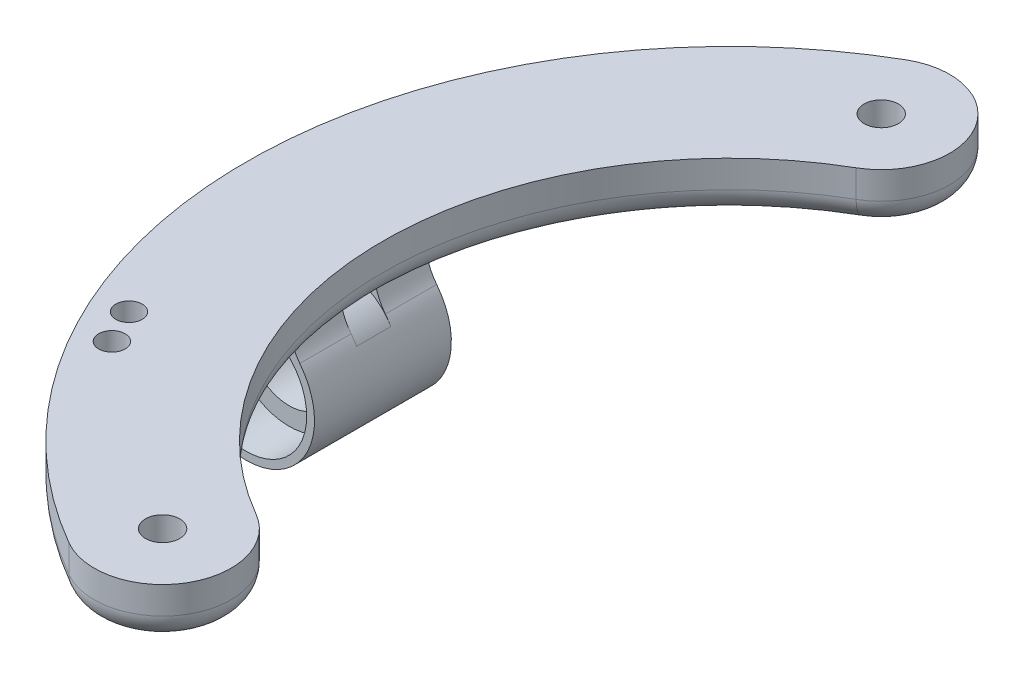
SolidWorks part; units mm, degrees
ref_plane "Front Plane" through (0, 0, 0) normal (0, 0, 1) x (1, 0, 0)
ref_plane "Top Plane" through (0, 0, 0) normal (0, 1, 0) x (1, 0, 0)
ref_plane "Right Plane" through (0, 0, 0) normal (1, 0, 0) x (0, 0, -1)
sketch "Sketch1" plane through (0, 0, 0) normal (0, 0, 1) x (1, 0, 0)
  line L0 (0, -6.6146) -> (0, 6.6146) construction
  line L1 (-64.2938, 0) -> (-64.2938, -5.08)
  line L2 (-69.0563, -9.8425) -> (-84.9312, -9.8425)
  line L3 (-89.6937, -5.08) -> (-89.6937, 0)
  line L4 (-89.6937, 0) -> (-64.2938, 0)
  line L5 (64.4709, -12.0559) -> (-64.2938, -9.8425) construction
  arc A0 (-84.9312, -9.8425) -> (-89.6937, -5.08) centre (-84.9312, -5.08) cw
  arc A1 (-69.0563, -9.8425) -> (-64.2938, -5.08) centre (-69.0563, -5.08) ccw
  point P4 (0, 0)
  point P8 (0, 0)
  point P12 (-89.6937, -9.8425)
  dimension "D4" = 4.7625
  dimension "D1" = 25.4
  dimension "D2" = 9.8425
  dimension "D3" = 128.5875
revolve "MainAttachmentRing" add sketch "Sketch1" angle 360 about L0
sketch "Sketch2" plane through (0, 0, 0) normal (0, 0, 1) x (1, 0, 0)
  line L5 (-76.9938, -9.8425) -> (-76.9938, -22.5425) construction
  line L6 (-76.9938, -22.5425) -> (-76.9938, -39.878) construction
  line L7 (0, 0) -> (0, -9.8425) construction
  line L8 (0, -9.8425) -> (-76.9938, -9.8425) construction
  line L9 (-69.0563, -8.7943) -> (-69.0563, -3.4925)
  line L10 (-69.0563, -9.8425) -> (-84.9312, -9.8425) construction
  line L11 (-84.9312, -8.7943) -> (-84.9312, -3.4925)
  line L13 (-69.0563, -9.8425) -> (69.0563, -9.8425) construction
  line L14 (-69.0563, -9.8425) -> (69.0563, -9.8425) construction
  line L18 (-84.9312, -9.8425) -> (84.9312, -9.8425) construction
  line L19 (-84.9312, -9.8425) -> (84.9312, -9.8425) construction
  line L20 (-69.0563, -3.4925) -> (-84.9312, -3.4925)
  line L21 (-84.9312, -31.9405) -> (-84.9312, -24.325) construction
  line L22 (-84.9312, -24.325) -> (-84.9312, -23.2606) construction
  line L24 (-69.0563, -24.325) -> (-69.0563, -23.2606) construction
  line L25 (-84.9312, -23.2606) -> (-84.9312, -12.6286) construction
  line L26 (-69.0563, -23.2606) -> (-69.0563, -12.6286) construction
  circle A2 centre (-76.9938, -22.5425) radius 2.3813 construction
  arc A5 (-86.9723, -14.6864) -> (-67.0152, -14.6864) centre (-76.9938, -22.5425) ccw
  circle A6 centre (-76.9938, -22.5425) radius 8.1352 construction
  arc A7 (-69.0563, -12.6286) -> (-76.9938, -9.8425) centre (-76.9938, -22.5425) ccw construction
  circle A8 centre (-76.9938, -22.5425) radius 7.9375
  arc A9 (-76.9938, -9.8425) -> (-84.9312, -12.6286) centre (-76.9938, -22.5425) ccw construction
  arc A10 (-69.0563, -8.7943) -> (-67.0152, -14.6864) centre (-59.5313, -8.7943) ccw
  arc A11 (-84.9312, -8.7943) -> (-86.9723, -14.6864) centre (-94.4562, -8.7943) cw
  circle A12 centre (-76.9938, -22.5425) radius 4 construction
  point P6 (-76.9938, -31.9405)
  point P27 (0, 0)
  dimension "D3" = 15.875
  dimension "D4" = 4.7625
  dimension "D6" = 9.525
  dimension "D5" = 8
  dimension "D7" = 12.7
  dimension "D1" = 6.35
  dimension "D2" = 12.7
extrude "SensorArmature" add sketch "Sketch2" along normal blind 12.7 and the other way blind 12.7 contours L11 A11 A5 A10 L9 L20 A12 region at (-68.9157, -12.0452, 0)
sketch "Sketch15" plane through (0, 0, 12.7) normal (0, 0, 1) x (1, 0, 0)
  circle A0 centre (-76.9938, -22.5425) radius 11.25
  dimension "D1" = 22.5
extrude "BearingRace1" cut sketch "Sketch15" against normal blind 8
sketch "Sketch16" plane through (0, 0, -12.7) normal (0, 0, -1) x (-1, 0, 0)
  circle A0 centre (76.9938, -22.5425) radius 11.25 construction
  circle A1 centre (76.9938, -22.5425) radius 11.25
extrude "BearingRace2" cut sketch "Sketch16" against normal blind 8
sketch "Sketch6" plane through (0, 0, 0) normal (0, 1, 0) x (1, 0, 0)
  line L0 (0, 0) -> (38.4252, 0) construction
  line L1 (68.0638, -50.8) -> (128.8023, -50.8)
  line L2 (66.0722, 0) -> (128.8023, 0) construction
  line L3 (66.0722, -53.3646) -> (66.0722, -20.0805)
  line L4 (68.0638, 50.8) -> (128.8023, 50.8)
  line L5 (128.8023, -50.8) -> (128.8023, 50.8)
  line L6 (66.0722, -20.0805) -> (66.0722, 0) construction
  line L7 (66.0722, 20.0805) -> (66.0722, 53.3646)
  line L8 (66.0722, 0) -> (66.0722, 20.0805) construction
  line L9 (66.0722, 53.3646) -> (66.0722, 60.6583) construction
  line L10 (66.0722, -60.6583) -> (66.0722, -53.3646) construction
  circle A0 centre (0, 0) radius 69.0563 construction
  circle A1 centre (0, 0) radius 89.6937 construction
  arc A2 (66.0722, -20.0805) -> (66.0722, 20.0805) centre (0, 0) ccw
  arc A3 (0, 69.0563) -> (66.0722, -20.0805) centre (0, 0) ccw construction
  arc A4 (66.0722, 20.0805) -> (0, 69.0563) centre (0, 0) ccw construction
  circle A5 centre (0, 0) radius 84.9312 construction
  arc A6 (68.0638, -50.8) -> (66.0722, -53.3646) centre (0, 0) ccw
  arc A7 (84.9312, 0) -> (66.0722, 53.3646) centre (0, 0) ccw construction
  arc A8 (66.0722, 53.3646) -> (68.0638, 50.8) centre (0, 0) ccw
  arc A9 (66.0722, -53.3646) -> (84.9312, 0) centre (0, 0) ccw construction
  arc A10 (0, 84.9312) -> (68.0638, -50.8) centre (0, 0) ccw construction
  arc A11 (68.0638, 50.8) -> (0, 84.9312) centre (0, 0) ccw construction
  point P2 (0, 0)
  point P3 (0, 0)
  point P4 (48.6828, 16.8474)
  point P11 (0, 0)
  point P14 (0, 0)
  point P15 (0, 0)
  dimension "D1" = 101.6
  dimension "D2" = 63.5
sketch "Sketch17" plane through (65.0875, 22.225, 0) normal (-1, 0, 0) x (0, 0, 1)
  line L0 (2.8259, -32.0675) -> (3.175, -32.0675)
  line L1 (3.175, -32.0675) -> (3.175, -33.655)
  line L2 (3.175, -33.655) -> (-3.175, -33.655)
  line L3 (-3.175, -33.655) -> (-3.175, -32.0675)
  line L4 (-3.175, -32.0675) -> (-2.8259, -32.0675)
  spline S0 degree 3 poles (-4002.7821, -32.0675) (-1334.2676, -32.0675) (1334.2468, -32.0675) (4002.7613, -32.0675) knots -707.720892 -707.720892 -707.720892 -707.720892 708.717209 708.717209 708.717209 708.717209 only from (-2.8259, -32.0675) to (2.8259, -32.0675) construction
  spline S1 degree 3 poles (-2.8259, -32.0675) (-0.942, -32.0675) (0.942, -32.0675) (2.8259, -32.0675) knots 0 0 0 0 1 1 1 1
  dimension "D1" = 1.5875
  dimension "D2" = 6.35
extrude "Cut-Extrude3" cut sketch "Sketch17" along normal through all
fillet "Fillet1" radius 9.525 2 edges at (-85.3032, -11.43, 0) (-68.6843, -11.43, 0)
sketch "Sketch19" plane through (0, -9.8425, 0) normal (0, -1, 0) x (1, 0, 0)
  line L0 (-76.4874, 12.7) -> (-76.4874, -12.7) construction
  line L1 (-83.9763, 12.7) -> (-68.9984, 12.7) construction
  line L2 (-83.9763, -12.7) -> (-68.9984, -12.7) construction
  line L3 (-83.9763, 12.7) -> (-68.9984, 12.7) construction
  line L4 (-83.9763, 15.875) -> (-68.9984, 15.875)
  line L5 (-83.9763, 28.575) -> (-78.6026, 28.575)
  line L6 (-76.4874, 15.875) -> (-76.4874, 28.575) construction
  line L7 (-83.9763, 15.875) -> (-83.9763, 28.575)
  line L8 (-68.9984, 23.6461) -> (-68.9984, 15.875)
  line L9 (-68.9984, 28.575) -> (-68.9984, 24.7775) construction
  line L10 (-70.9492, 28.575) -> (-68.9984, 28.575) construction
  line L11 (-83.9763, 28.575) -> (-68.9984, 28.575) construction
  line L12 (-74.361, 28.575) -> (-70.9492, 28.575) construction
  circle A0 centre (0, 0) radius 76.4874 construction
  arc A1 (-62.0003, 39.1237) -> (-67.3705, 42.5124) centre (-64.6854, 40.818) ccw
  arc A2 (-67.3705, 42.5124) -> (-72.7997, 32.3466) centre (0, 0) ccw
  arc A3 (-62.0003, 39.1237) -> (-68.5893, 25.8884) centre (0, 0) ccw
  arc A4 (-78.6435, 12.7) -> (-67.3705, 42.5124) centre (0, 0) ccw construction
  circle A5 centre (0, 0) radius 79.6624 construction
  arc A6 (-72.204, 12.7) -> (-62.0003, 39.1237) centre (0, 0) ccw construction
  circle A7 centre (0, 0) radius 73.3124 construction
  arc A8 (-68.9984, 24.7775) -> (-71.573, 15.875) centre (0, 0) ccw construction
  arc A9 (-71.573, 15.875) -> (-72.204, 12.7) centre (0, 0) ccw construction
  arc A10 (-74.361, 28.575) -> (-76.4874, 22.266) centre (0, 0) ccw construction
  arc A11 (-76.4874, 22.266) -> (-78.0646, 15.875) centre (0, 0) ccw construction
  arc A12 (-78.0646, 15.875) -> (-78.6435, 12.7) centre (0, 0) ccw construction
  arc A13 (-66.3237, 38.0983) -> (-62.0003, 39.1237) centre (-64.6854, 40.818) ccw construction
  arc A14 (-67.3705, 42.5124) -> (-66.3237, 38.0983) centre (-64.6854, 40.818) ccw construction
  arc A15 (-72.7997, 32.3466) -> (-78.6026, 28.575) centre (-78.6026, 34.925) cw
  arc A16 (-68.5893, 25.8884) -> (-68.9984, 23.6461) centre (-62.6484, 23.6461) ccw
  point P9 (-76.4874, 0)
  point P17 (0, 0)
  dimension "D3" = 6.35
  dimension "D6" = 6.35
  dimension "D1" = 3.175
  dimension "D2" = 12.7
  dimension "D4" = 3.175
  dimension "D5" = 3.175
extrude "Cut-Extrude5" cut sketch "Sketch19" against normal blind 6.35
hole_wizard "#10 (0.1935) Diameter Hole1" positions "Sketch25" profile "Sketch24" hole size "#10" standard "ANSI Inch" end condition through all
sketch "Sketch25" plane through (0, -9.8425, 0) normal (0, -1, 0) x (-1, 0, 0)
  line L0 (83.9763, -28.575) -> (83.9763, -15.875) construction
  line L1 (83.9763, -28.575) -> (83.9763, -15.875) construction
  line L2 (83.9763, -15.875) -> (68.9984, -15.875) construction
  line L3 (83.9763, -15.875) -> (68.9984, -15.875) construction
  line L4 (76.4874, -15.875) -> (76.4874, -34.925) construction
  line L6 (83.9763, -28.575) -> (76.4874, -28.575) construction
  line L7 (76.4874, -28.575) -> (73.3124, -28.575) construction
  line L8 (73.3124, -28.575) -> (73.3124, -41.275) construction
  point P0 (73.3124, -41.275)
  point P2 (76.4874, -34.925)
  point P21 (71.7249, -41.275)
  point P22 (76.4874, -34.925)
  dimension "D1" = 19.05
  dimension "D2" = 12.7
  dimension "D3" = 3.175
sketch "Sketch24" plane through (-73.3124, -9.8425, 41.275) normal (1, 0, 0) x (0, 0, -1)
  line L0 (0, 0) -> (0, 9.8425)
  line L1 (0, 9.8425) -> (2.4574, 9.8425)
  line L2 (2.4574, 9.8425) -> (2.4574, 0)
  line L5 (2.4574, 0) -> (0, 0)
  line L11 (0, -6.35) -> (0, 107.95) construction
  dimension "Thru Hole Dia." = 4.9149
  dimension "Thru Hole Depth" = 9.8425
hole_wizard "1/4 (0.25) Diameter Hole1" positions "Sketch26" profile "Sketch27" hole size "1/4" standard "ANSI Inch" end condition through all
sketch "Sketch26" plane through (0, -9.8425, 0) normal (0, -1, 0) x (-1, 0, 0)
  line L0 (0, 0) -> (-76.9938, 0) construction
  arc A3 (76.9293, 3.1508) -> (76.9293, -3.1508) centre (0, 0) ccw
  arc A4 (76.9293, 3.1508) -> (76.9293, -3.1508) centre (0, 0) ccw construction
  point P0 (-76.9938, 0)
  point P30 (38.4969, 66.6785)
  point P31 (38.4969, -66.6785)
  point P32 (0, 0)
  dimension "D1" = 7.9375
  dimension "D2" = 3
sketch "Sketch27" plane through (76.9938, -9.8425, 0) normal (1, 0, 0) x (0, 0, -1)
  line L0 (0, 0) -> (0, 9.8425)
  line L1 (0, 9.8425) -> (3.175, 9.8425)
  line L2 (3.175, 9.8425) -> (3.175, 0.635)
  line L3 (3.175, 0.635) -> (3.81, 0)
  line L5 (3.81, 0) -> (0, 0)
  line L6 (-3.175, 0.635) -> (-3.81, 0) construction
  line L11 (0, -6.35) -> (0, 107.95) construction
  dimension "Thru Hole Dia." = 6.35
  dimension "Thru Hole Depth" = 9.8425
  dimension "Near C'Sink Dia." = 7.62
  dimension "Near C'Sink Angle" = 90
sketch "Sketch28" plane through (0, 0, 0) normal (0, 1, 0) x (1, 0, 0)
  line L0 (0, 0) -> (-32.1469, 55.68)
  line L1 (-52.6413, 91.1774) -> (62.9712, 117.188)
  line L2 (62.9712, 117.188) -> (148.9034, 11.6303)
  line L3 (148.9034, 11.6303) -> (-6.9891, -155.4639)
  line L4 (-6.9891, -155.4639) -> (-55.4139, -95.9797)
  line L5 (-55.4139, -95.9797) -> (-44.8469, -77.6771)
  line L6 (-38.4969, -66.6785) -> (-32.1469, -55.68) construction
  line L7 (-32.1469, -55.68) -> (0, 0)
  line L8 (-44.8469, -77.6771) -> (-38.4969, -66.6785) construction
  line L9 (-32.1469, 55.68) -> (-38.4969, 66.6785) construction
  line L10 (-44.8469, 77.6771) -> (-52.6413, 91.1774)
  line L11 (-38.4969, 66.6785) -> (-44.8469, 77.6771) construction
  circle A2 centre (0, 0) radius 76.9937
  circle A3 centre (0, 0) radius 76.9937 construction
  arc A4 (-32.1469, 55.68) -> (-44.8469, 77.6771) centre (-38.4969, 66.6785) ccw
  arc A5 (-44.8469, -77.6771) -> (-32.1469, -55.68) centre (-38.4969, -66.6785) ccw
  arc A6 (-32.1469, -55.68) -> (-48.9342, -59.4431) centre (-38.4969, -66.6785) ccw construction
  arc A7 (-48.9342, -59.4431) -> (-44.8469, -77.6771) centre (-38.4969, -66.6785) ccw construction
  arc A8 (-44.8469, 77.6771) -> (-48.9342, 59.4431) centre (-38.4969, 66.6785) ccw construction
  arc A9 (-48.9342, 59.4431) -> (-32.1469, 55.68) centre (-38.4969, 66.6785) ccw construction
  point P14 (-56.1942, -95.5249)
  dimension "D1" = 12.7
extrude "Cut-Extrude6" cut sketch "Sketch28" against normal through all both and the other way through all
fillet "Fillet2" radius 4.7625 2 edges at (-27.1119, -9.8425, 72.3063) (-27.1119, -9.8425, -72.3063)
